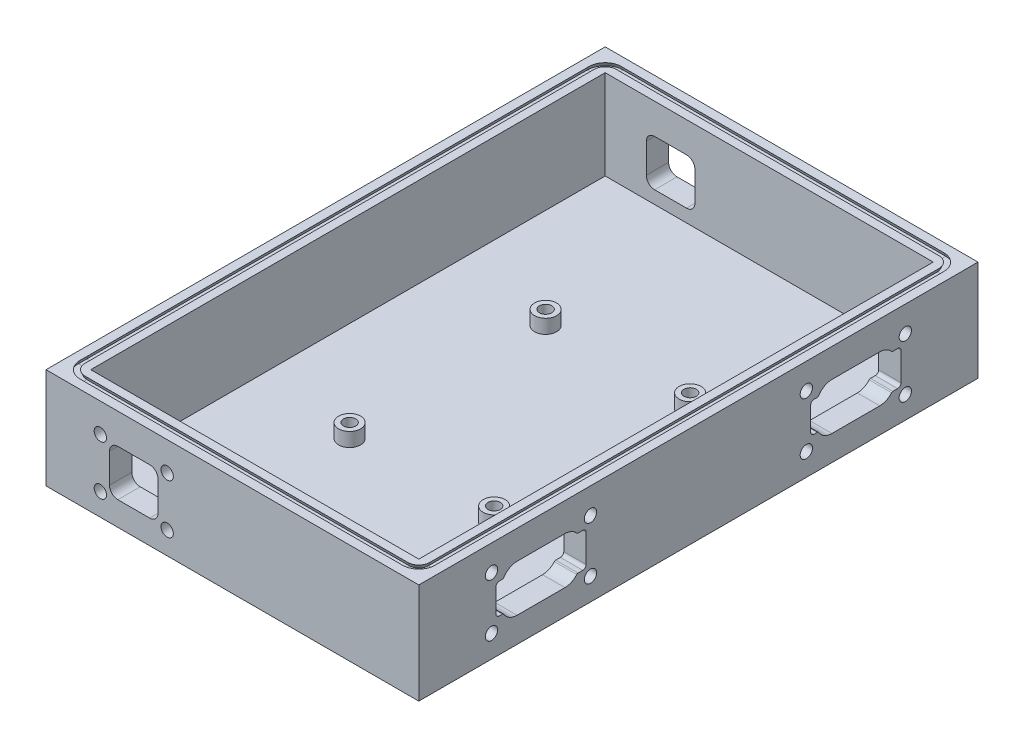
SolidWorks part; units mm, degrees
ref_plane "Front Plane" through (0, 0, 0) normal (0, 0, 1) x (1, 0, 0)
ref_plane "Top Plane" through (0, 0, 0) normal (0, 1, 0) x (1, 0, 0)
ref_plane "Right Plane" through (0, 0, 0) normal (1, 0, 0) x (0, 0, -1)
sketch "Sketch1" plane through (0, 0, 0) normal (0, 1, 0) x (1, 0, 0)
  line L1 (0, 0) -> (169.3418, 0)
  line L2 (0, 0) -> (0, 254)
  line L3 (0, 254) -> (169.3418, 254)
  line L4 (169.3418, 0) -> (169.3418, 254)
  dimension "D1" = 169.3418
  dimension "D2" = 254
extrude "Boss-Extrude1" add sketch "Sketch1" along normal blind 45.72
sketch "12 pin hole" [suppressed] plane through (254, 0, 0) normal (1, 0, 0) x (0, 0, -1)
  line L8 (50.8, 10.16) -> (95.758, 10.16) construction
  line L9 (50.8, 10.16) -> (50.8, 34.036) construction
  line L10 (50.8, 34.036) -> (95.758, 34.036) construction
  line L11 (95.758, 10.16) -> (95.758, 34.036) construction
  line L12 (55.7357, 28.956) -> (54.2925, 28.956)
  line L13 (52.7685, 27.432) -> (52.7685, 16.764)
  line L14 (54.2925, 15.24) -> (55.7357, 15.24)
  line L16 (90.087, 29.972) -> (92.2655, 29.972)
  line L17 (93.7895, 28.448) -> (93.7895, 15.748)
  line L18 (92.2655, 14.224) -> (90.087, 14.224)
  line L21 (62.4205, 25.654) -> (84.1375, 25.654) construction
  line L22 (62.4205, 25.654) -> (62.4205, 18.542) construction
  line L23 (62.4205, 18.542) -> (84.1375, 18.542) construction
  line L24 (84.1375, 25.654) -> (84.1375, 18.542) construction
  line L25 (62.4205, 32.7152) -> (84.1375, 32.7152)
  line L26 (62.4205, 11.4808) -> (84.1375, 11.4808)
  line L27 (52.7685, 22.098) -> (50.8, 22.098) construction
  line L28 (93.7895, 22.098) -> (95.758, 22.098) construction
  arc A4 (62.4205, 32.7152) -> (56.3868, 29.3222) centre (62.4205, 25.654) ccw
  arc A5 (89.5075, 30.2392) -> (84.1375, 32.7152) centre (84.1375, 25.654) ccw
  arc A6 (62.4205, 11.4808) -> (56.3868, 14.8738) centre (62.4205, 18.542) cw
  arc A7 (89.5075, 13.9568) -> (84.1375, 11.4808) centre (84.1375, 18.542) cw
  arc A8 (90.087, 29.972) -> (89.5075, 30.2392) centre (90.087, 30.734) cw
  arc A9 (90.087, 14.224) -> (89.5075, 13.9568) centre (90.087, 13.462) ccw
  arc A10 (55.7357, 15.24) -> (56.3868, 14.8738) centre (55.7357, 14.478) cw
  arc A11 (55.7357, 28.956) -> (56.3868, 29.3222) centre (55.7357, 29.718) ccw
  arc A12 (92.2655, 29.972) -> (93.7895, 28.448) centre (92.2655, 28.448) cw
  arc A13 (93.7895, 15.748) -> (92.2655, 14.224) centre (92.2655, 15.748) cw
  arc A14 (52.7685, 16.764) -> (54.2925, 15.24) centre (54.2925, 16.764) ccw
  arc A15 (54.2925, 28.956) -> (52.7685, 27.432) centre (54.2925, 27.432) ccw
  point P25 (50.8, 22.098)
  point P28 (52.7685, 22.098)
  point P29 (93.7895, 22.098)
  point P34 (62.4205, 22.098)
  point P35 (84.1375, 22.098)
  point P44 (73.279, 10.16)
  point P46 (73.279, 11.4808)
  point P59 (93.7895, 29.972)
  point P62 (93.7895, 14.224)
  point P65 (52.7685, 15.24)
  point P68 (52.7685, 28.956)
  dimension "D4" = 41.021
  dimension "D5" = 15.748
  dimension "D11" = 7.0612
  dimension "D12" = 0.762
  dimension "D13" = 1.524
  dimension "D1" = 44.958
  dimension "D2" = 23.876
  dimension "D8" = 13.716
  dimension "D9" = 21.2344
  dimension "D10" = 21.717
sketch "Sketch2" plane through (0, 45.72, 0) normal (0, 1, 0) x (1, 0, 0)
  line L0 (0, 254) -> (0, 0) construction
  line L1 (10.16, 10.16) -> (159.1818, 10.16)
  line L2 (10.16, 10.16) -> (10.16, 243.84)
  line L3 (10.16, 243.84) -> (159.1818, 243.84)
  line L4 (159.1818, 10.16) -> (159.1818, 243.84)
  line L5 (169.3418, 254) -> (0, 254) construction
  line L6 (169.3418, 0) -> (169.3418, 254) construction
  line L7 (0, 0) -> (169.3418, 0) construction
  dimension "D1" = 10.16
  dimension "D2" = 10.16
  dimension "D3" = 10.16
  dimension "D4" = 10.16
extrude "Cut-Extrude1" cut sketch "Sketch2" against normal blind 40.64
ref_plane "Plane1" through (0, 45.72, 0) normal (0, 1, 0) x (1, 0, 0)
sketch "Sketch3" plane through (0, 45.72, 0) normal (0, 1, 0) x (1, 0, 0)
  line L4 (6.35, 11.43) -> (6.35, 242.57)
  line L5 (159.1818, 243.84) -> (10.16, 243.84) construction
  line L6 (10.16, 243.84) -> (10.16, 10.16) construction
  line L7 (159.1818, 10.16) -> (159.1818, 243.84) construction
  line L8 (10.16, 10.16) -> (159.1818, 10.16) construction
  line L13 (11.43, 247.65) -> (157.9118, 247.65)
  line L14 (162.9918, 242.57) -> (162.9918, 11.43)
  line L15 (157.9118, 6.35) -> (11.43, 6.35)
  arc A0 (6.35, 242.57) -> (11.43, 247.65) centre (11.43, 242.57) cw
  arc A1 (157.9118, 247.65) -> (162.9918, 242.57) centre (157.9118, 242.57) cw
  arc A2 (162.9918, 11.43) -> (157.9118, 6.35) centre (157.9118, 11.43) cw
  arc A3 (11.43, 6.35) -> (6.35, 11.43) centre (11.43, 11.43) cw
  dimension "D5" = 5.08
  dimension "D1" = 3.81
  dimension "D2" = 3.81
  dimension "D3" = 3.81
  dimension "D4" = 3.81
ref_plane "Plane2" through (0, 0, 0) normal (0, 0, 1) x (1, 0, 0)
ref_plane "Plane3" through (0, 0, -15.24) normal (0, 0, 1) x (1, 0, 0)
sketch "Sketch4" plane through (0, 0, -15.24) normal (0, 0, 1) x (1, 0, 0)
  line L0 (4.064, 45.72) -> (3.2724, 43.942)
  line L1 (6.35, 45.72) -> (7.1416, 43.942)
  line L2 (3.2724, 43.942) -> (7.1416, 43.942)
  line L5 (4.064, 45.72) -> (6.35, 45.72)
  dimension "D1" = 1.778
  dimension "D2" = 2.286
  dimension "D3" = 66
  dimension "D4" = 66
sweep "Cut-Sweep2" cut profiles "Sketch4" path "Sketch3"
sketch "Sketch13" plane through (169.3418, 0, 0) normal (1, 0, 0) x (0, 0, -1)
  line L0 (33.02, 10.16) -> (33.02, 0) construction
  line L1 (0, 0) -> (254, 0) construction
  line L2 (33.02, 10.16) -> (0, 10.16) construction
  line L3 (0, 45.72) -> (0, 0) construction
  line L4 (220.98, 0) -> (220.98, 10.16) construction
  line L5 (220.98, 10.16) -> (254, 10.16) construction
  line L6 (254, 45.72) -> (254, 0) construction
  line B0 (33.02, 10.16) -> (77.978, 10.16) construction
  line B1 (33.02, 10.16) -> (33.02, 34.036) construction
  line B2 (33.02, 34.036) -> (77.978, 34.036) construction
  line B3 (77.978, 10.16) -> (77.978, 34.036) construction
  line B4 (37.9557, 28.956) -> (36.5125, 28.956)
  line B5 (34.9885, 27.432) -> (34.9885, 16.764)
  line B6 (36.5125, 15.24) -> (37.9557, 15.24)
  line B7 (72.307, 29.972) -> (74.4855, 29.972)
  line B8 (76.0095, 28.448) -> (76.0095, 15.748)
  line B9 (74.4855, 14.224) -> (72.307, 14.224)
  line B10 (44.6405, 32.7152) -> (66.3575, 32.7152)
  line B11 (44.6405, 11.4808) -> (66.3575, 11.4808)
  arc B12 (44.6405, 32.7152) -> (38.6068, 29.3222) centre (44.6405, 25.654) ccw
  arc B13 (71.7275, 30.2392) -> (66.3575, 32.7152) centre (66.3575, 25.654) ccw
  arc B14 (44.6405, 11.4808) -> (38.6068, 14.8738) centre (44.6405, 18.542) cw
  arc B15 (71.7275, 13.9568) -> (66.3575, 11.4808) centre (66.3575, 18.542) cw
  arc B16 (72.307, 29.972) -> (71.7275, 30.2392) centre (72.307, 30.734) cw
  arc B17 (72.307, 14.224) -> (71.7275, 13.9568) centre (72.307, 13.462) ccw
  arc B18 (37.9557, 15.24) -> (38.6068, 14.8738) centre (37.9557, 14.478) cw
  arc B19 (37.9557, 28.956) -> (38.6068, 29.3222) centre (37.9557, 29.718) ccw
  arc B20 (74.4855, 29.972) -> (76.0095, 28.448) centre (74.4855, 28.448) cw
  arc B21 (76.0095, 15.748) -> (74.4855, 14.224) centre (74.4855, 15.748) cw
  arc B22 (34.9885, 16.764) -> (36.5125, 15.24) centre (36.5125, 16.764) ccw
  arc B23 (36.5125, 28.956) -> (34.9885, 27.432) centre (36.5125, 27.432) ccw
  line B24 (176.022, 10.16) -> (220.98, 10.16) construction
  line B25 (176.022, 10.16) -> (176.022, 34.036) construction
  line B26 (176.022, 34.036) -> (220.98, 34.036) construction
  line B27 (220.98, 10.16) -> (220.98, 34.036) construction
  line B28 (180.9577, 28.956) -> (179.5145, 28.956)
  line B29 (177.9905, 27.432) -> (177.9905, 16.764)
  line B30 (179.5145, 15.24) -> (180.9577, 15.24)
  line B31 (215.309, 29.972) -> (217.4875, 29.972)
  line B32 (219.0115, 28.448) -> (219.0115, 15.748)
  line B33 (217.4875, 14.224) -> (215.309, 14.224)
  line B34 (187.6425, 32.7152) -> (209.3595, 32.7152)
  line B35 (187.6425, 11.4808) -> (209.3595, 11.4808)
  arc B36 (187.6425, 32.7152) -> (181.6088, 29.3222) centre (187.6425, 25.654) ccw
  arc B37 (214.7295, 30.2392) -> (209.3595, 32.7152) centre (209.3595, 25.654) ccw
  arc B38 (187.6425, 11.4808) -> (181.6088, 14.8738) centre (187.6425, 18.542) cw
  arc B39 (214.7295, 13.9568) -> (209.3595, 11.4808) centre (209.3595, 18.542) cw
  arc B40 (215.309, 29.972) -> (214.7295, 30.2392) centre (215.309, 30.734) cw
  arc B41 (215.309, 14.224) -> (214.7295, 13.9568) centre (215.309, 13.462) ccw
  arc B42 (180.9577, 15.24) -> (181.6088, 14.8738) centre (180.9577, 14.478) cw
  arc B43 (180.9577, 28.956) -> (181.6088, 29.3222) centre (180.9577, 29.718) ccw
  arc B44 (217.4875, 29.972) -> (219.0115, 28.448) centre (217.4875, 28.448) cw
  arc B45 (219.0115, 15.748) -> (217.4875, 14.224) centre (217.4875, 15.748) cw
  arc B46 (177.9905, 16.764) -> (179.5145, 15.24) centre (179.5145, 16.764) ccw
  arc B47 (179.5145, 28.956) -> (177.9905, 27.432) centre (179.5145, 27.432) ccw
  dimension "D1" = 33.02
  dimension "D2" = 10.16
sketch_block_instance "Block7-3"
sketch_block "Block7" parameters "D6"=7.0612, "D7"=0.762, "D8"=1.524, "D1"=44.958, "D2"=23.876, "D3"=41.021, "D4"=21.2344, "D5"=21.717
sketch_block_instance "Block7-4"
extrude "Cut-Extrude10" cut sketch "Sketch13" against normal up to next
sketch "12 pin mount" plane through (169.3418, 0, 0) normal (1, 0, 0) x (0, 0, -1)
  circle A0 centre (77.978, 34.036) radius 2.8
  circle A1 centre (77.978, 10.16) radius 2.8
  circle A2 centre (33.02, 10.16) radius 2.8
  circle A3 centre (33.02, 34.036) radius 2.8
  circle A4 centre (176.022, 34.036) radius 2.8
  circle A5 centre (220.98, 34.036) radius 2.8
  circle A6 centre (220.98, 10.16) radius 2.8
  circle A7 centre (176.022, 10.16) radius 2.8
  dimension "D1" = 5.6
extrude "Cut-Extrude3" cut sketch "12 pin mount" against normal blind 5.5
sketch "4 pin connector" plane through (0, 0, 0) normal (0, 0, 1) x (1, 0, 0)
  line L0 (55.0418, 0) -> (55.0418, 10.16) construction
  line L1 (0, 0) -> (169.3418, 0) construction
  line L2 (55.0418, 10.16) -> (169.3418, 10.16) construction
  line L3 (169.3418, 45.72) -> (169.3418, 0) construction
  line L5 (24.6888, 32.6136) -> (55.0418, 32.6136) construction
  line L6 (24.6888, 32.6136) -> (24.6888, 10.16) construction
  line L7 (24.6888, 10.16) -> (55.0418, 10.16) construction
  line L8 (55.0418, 32.6136) -> (55.0418, 10.16) construction
  line L9 (32.6263, 31.877) -> (47.1043, 31.877)
  line L10 (28.8163, 28.067) -> (28.8163, 14.7066)
  line L11 (32.6263, 10.8966) -> (47.1043, 10.8966)
  line L12 (50.9143, 28.067) -> (50.9143, 14.7066)
  line L13 (39.8653, 10.8966) -> (39.8653, 31.877) construction
  line L14 (28.8163, 21.3868) -> (50.9143, 21.3868) construction
  arc A0 (47.1043, 31.877) -> (50.9143, 28.067) centre (47.1043, 28.067) cw
  arc A1 (47.1043, 10.8966) -> (50.9143, 14.7066) centre (47.1043, 14.7066) ccw
  arc A2 (28.8163, 14.7066) -> (32.6263, 10.8966) centre (32.6263, 14.7066) ccw
  arc A3 (32.6263, 31.877) -> (28.8163, 28.067) centre (32.6263, 28.067) ccw
  point P4 (39.8653, 21.3868)
  point P12 (39.8653, 10.16)
  point P15 (55.0418, 21.3868)
  point P20 (50.9143, 31.877)
  point P24 (50.9143, 10.8966)
  point P29 (28.8163, 31.877)
  dimension "D1" = 22.098
  dimension "D7" = 3.81
  dimension "D2" = 22.4536
  dimension "D3" = 30.353
  dimension "D4" = 10.16
  dimension "D5" = 114.3
  dimension "D6" = 20.9804
extrude "Cut-Extrude5" cut sketch "4 pin connector" against normal up to next
extrude "Cut-Extrude6" cut sketch "Sketch5<2>" along normal up to next from surface starting at face at (84.6709, 22.86, -254)
sketch "Sketch5<2>" plane through (0, 0, 0) normal (0, 0, 1) x (1, 0, 0) same geometry as "4 pin connector"
sketch "Sketch6" plane through (0, 0, 0) normal (0, 0, 1) x (1, 0, 0)
  circle A0 centre (55.0418, 32.6136) radius 2.8
  circle A1 centre (55.0418, 10.16) radius 2.8
  circle A2 centre (24.6888, 10.16) radius 2.8
  circle A3 centre (24.6888, 32.6136) radius 2.8
  dimension "D1" = 5.6
extrude "Cut-Extrude7" cut sketch "Sketch6" against normal blind 5.5
extrude "Cut-Extrude8" cut sketch "Sketch6<2>" along normal blind 5.5 from surface starting at face at (39.8653, 21.3868, -254)
sketch "Sketch6<2>" plane through (0, 0, 0) normal (0, 0, 1) x (1, 0, 0) same geometry as "Sketch6"
sketch "Sketch7" plane through (0, 5.08, 0) normal (0, 1, 0) x (1, 0, 0)
  line L0 (121.0818, 127) -> (159.1818, 127) construction
  line L1 (159.1818, 10.16) -> (159.1818, 243.84) construction
  line L2 (159.1818, 10.16) -> (159.1818, 243.84) construction
  line L5 (121.0818, 82.485) -> (55.4218, 82.485) construction
  line L6 (121.0818, 82.485) -> (121.0818, 171.515) construction
  line L7 (121.0818, 171.515) -> (55.4218, 171.515) construction
  line L8 (55.4218, 82.485) -> (55.4218, 171.515) construction
  circle A0 centre (55.4218, 82.485) radius 5
  circle A1 centre (121.0818, 82.485) radius 5
  circle A2 centre (121.0818, 171.515) radius 5
  circle A3 centre (55.4218, 171.515) radius 5
  dimension "D1" = 10
  dimension "D2" = 89.03
  dimension "D3" = 65.66
  dimension "D4" = 38.1
sketch "Sketch8" plane through (0, 5.08, 0) normal (0, 1, 0) x (1, 0, 0)
  circle A0 centre (55.4218, 171.515) radius 2.8
  circle A1 centre (121.0818, 171.515) radius 2.8
  circle A2 centre (121.0818, 82.485) radius 2.8
  circle A3 centre (55.4218, 82.485) radius 2.8
  dimension "D1" = 5.6
extrude "Boss-Extrude2" add sketch "Sketch7" along normal blind 6.35
extrude "Cut-Extrude9" cut sketch "Sketch8" against normal blind 5.5 from surface starting at face at (121.0818, 11.43, -77.485)
equation "\"M4 insert  width\"= 5.6mm"
equation "\"M4 insert  depth\"= 5.5mm"
equation "\"depth\"=0.1"
